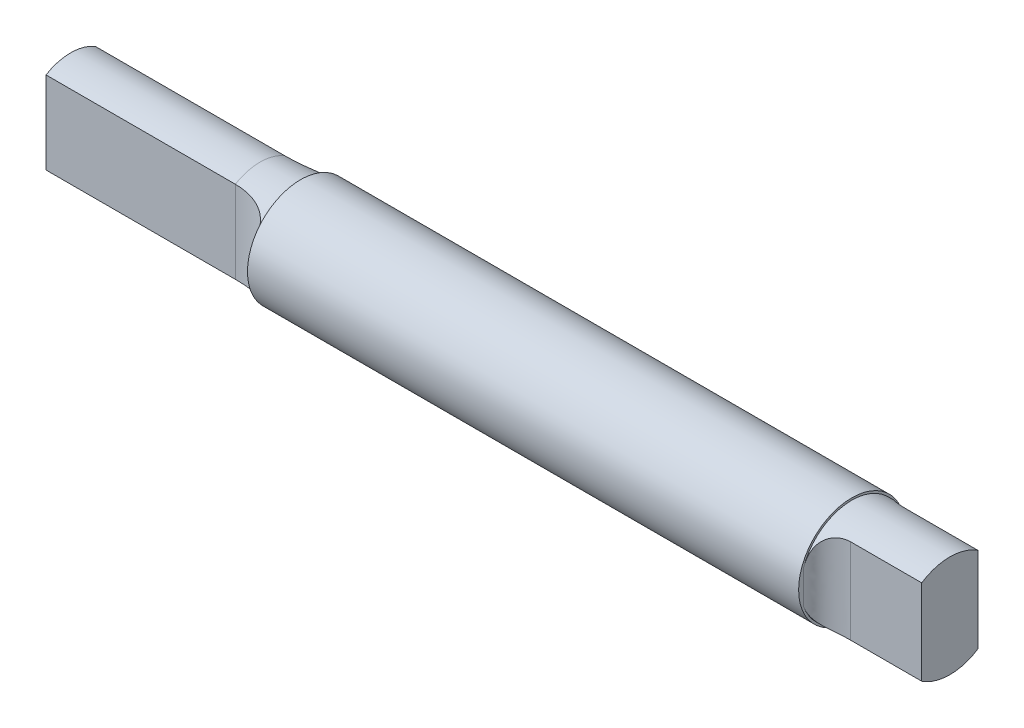
SolidWorks part; units mm, degrees
ref_plane "Front" through (0, 0, 0) normal (0, 0, 1) x (1, 0, 0)
ref_plane "Top" through (0, 0, 0) normal (0, 1, 0) x (1, 0, 0)
ref_plane "Right" through (0, 0, 0) normal (1, 0, 0) x (0, 0, -1)
sketch "Sketch1" plane through (0, 0, 0) normal (0, 1, 0) x (1, 0, 0)
  line L1 (0, 0) -> (65, 0)
  line L2 (0, 0) -> (0, -3.93)
  line L3 (0, -3.93) -> (65, -3.93)
  line L4 (65, 0) -> (65, -3.93)
  dimension "D1" = 65
  dimension "D2" = 3.93
revolve "Revolve1" add sketch "Sketch1" angle 360 about L3
sketch "Sketch2" plane through (65, 0, 0) normal (1, 0, 0) x (0, 0, -1)
  line L0 (-3.93, 3.93) -> (-3.93, -3.93) construction
  line L1 (-7.86, 0) -> (0, 0) construction
  line L2 (-6.0104, 3.15) -> (-6.0104, -3.15)
  line L3 (-1.8496, 3.15) -> (-1.8496, -3.15)
  circle A0 centre (-3.93, 0) radius 3.93 construction
  circle A1 centre (-3.93, 0) radius 3.775
  circle M4 centre (-3.93, 0) radius 3.93
  dimension "D1" = 7.55
  dimension "D2" = 6.3
extrude "Cut-Extrude1" cut sketch "Sketch2" against normal blind 6.2515 contours L3 A1 | L2 A1 | A1 M4 region at (65, 0, 6.7033) region at (65, 0, 1.1567) region at (65, 0, 7.7488)
sketch "Sketch3" plane through (0, 0, 1.8496) normal (0, 0, -1) x (-1, 0, 0)
  line L0 (0, -3.93) -> (-65, -3.93) construction
  line L1 (-32.5, -3.93) -> (-32.5, 10.1746) construction
ref_plane "Plane1" through (32.5, 0, 0) normal (1, 0, 0) x (0, 0, -1)
mirror "Mirror3" about plane through (32.5, 0, 0) normal (1, 0, 0) of "Cut-Extrude1"
sketch "Sketch4" plane through (6.2515, 0, 0) normal (-1, 0, 0) x (0, 0, 1)
  line L0 (2.085, 3.0913) -> (2.085, -3.0913)
  line L1 (5.775, 3.0913) -> (5.775, -3.0913)
  line L6 (2.085, 0) -> (5.775, 0) construction
  arc A0 (5.775, 3.0913) -> (2.085, 3.0913) centre (3.93, 0) ccw
  circle A1 centre (3.93, 0) radius 3.93
  circle A2 centre (3.93, 0) radius 3.93
  arc A3 (2.085, -3.0913) -> (5.775, -3.0913) centre (3.93, 0) ccw
  line M6 (1.8496, -3.15) -> (1.8496, 3.15)
  arc M7 (1.8496, 3.15) -> (6.0104, 3.15) centre (3.93, 0) cw
  line M8 (6.0104, 3.15) -> (6.0104, -3.15)
  arc M9 (6.0104, -3.15) -> (1.8496, -3.15) centre (3.93, 0) cw
  circle M10 centre (3.93, 0) radius 3.93
  dimension "D2" = 7.2
  dimension "D3" = 3.69
  dimension "D1" = 0
extrude "Cut-Extrude2" cut sketch "Sketch4" against normal blind 8.7485 contours M10 M9 M6 M7 M8 region at (6.2515, 0, 0.1112)
sketch "Sketch5" plane through (0, 0, 0) normal (-1, 0, 0) x (0, 0, 1)
  line L0 (2.105, 3.045) -> (2.105, -3.045)
  line L1 (5.755, 3.045) -> (5.755, -3.045)
  line L2 (2.105, 0) -> (5.755, 0) construction
  arc A0 (5.755, 3.045) -> (2.105, 3.045) centre (3.93, 0) ccw
  arc A1 (2.105, -3.045) -> (5.755, -3.045) centre (3.93, 0) ccw
  circle A2 centre (3.93, 0) radius 3.93 construction
  circle A3 centre (3.93, 0) radius 3.93
  dimension "D1" = 7.1
  dimension "D2" = 3.65
extrude "Cut-Extrude3" cut sketch "Sketch5" against normal blind 17
sketch "Sketch6" plane through (58.7485, 0, 0) normal (1, 0, 0) x (0, 0, -1)
  line L2 (-1.8496, -3.15) -> (-1.8496, 3.15)
  line L3 (-6.0104, 3.15) -> (-6.0104, -3.15)
  line L4 (-1.8496, -3.15) -> (-1.8496, 3.15)
  line L5 (-6.0104, 3.15) -> (-6.0104, -3.15)
  circle A1 centre (-3.93, 0) radius 3.93
  circle A2 centre (-3.93, 0) radius 3.93
  arc A4 (-6.0104, -3.15) -> (-1.8496, -3.15) centre (-3.93, 0) ccw
  arc A5 (-1.8496, 3.15) -> (-6.0104, 3.15) centre (-3.93, 0) ccw
  arc A6 (-6.0104, -3.15) -> (-1.8496, -3.15) centre (-3.93, 0) ccw
  arc A7 (-1.8496, 3.15) -> (-6.0104, 3.15) centre (-3.93, 0) ccw
  dimension "D1" = 0
  dimension "D2" = 0
extrude "Cut-Extrude4" cut sketch "Sketch6" against normal blind 1
fillet "Fillet1" radius 1.5 2 edges at (57.7485, 0, 1.8496) (57.7485, 0, 6.0104) second distance 2 first distance on face at (57.7485, 0, 3.93)
fillet "Fillet2" radius 1.5 2 edges at (17, 0, 5.755) (17, 0, 2.105) second distance 3 first distance on face at (17, 0, 3.93)
fillet "Fillet3" radius 0.2 2 edges second distance 3 first distance on face at (17, 0, 3.93)
